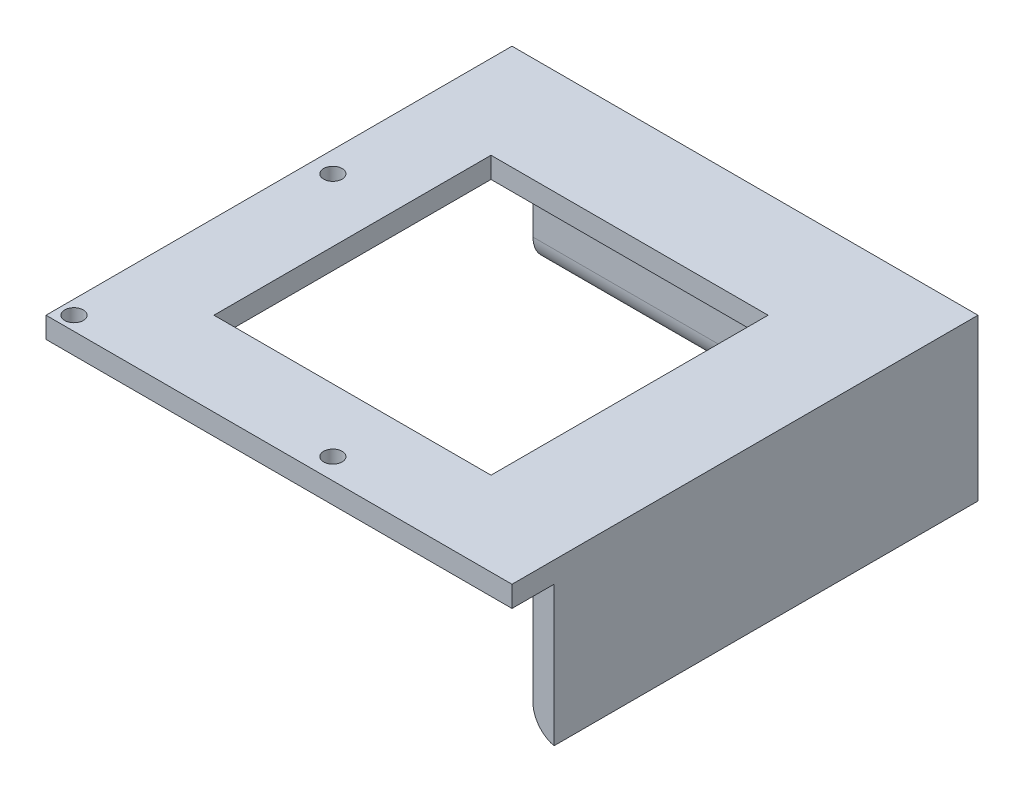
SolidWorks part; units mm, degrees
ref_plane "Front Plane" through (0, 0, 0) normal (0, 0, 1) x (1, 0, 0)
ref_plane "Top Plane" through (0, 0, 0) normal (0, 1, 0) x (1, 0, 0)
ref_plane "Right Plane" through (0, 0, 0) normal (1, 0, 0) x (0, 0, -1)
sketch "Sketch1" plane through (0, 0, 0) normal (0, 1, 0) x (1, 0, 0)
  line L9 (9.525, 9.525) -> (100.965, 9.525) construction
  line L10 (9.525, 9.525) -> (9.525, 100.965) construction
  line L11 (9.525, 100.965) -> (100.965, 100.965) construction
  line L12 (100.965, 9.525) -> (100.965, 100.965) construction
  line L16 (9.525, 100.965) -> (9.525, 105.7275) construction
  line L17 (0, 0) -> (105.7275, 0) construction
  line L18 (0, 0) -> (0, 105.7275) construction
  line L19 (0, 105.7275) -> (105.7275, 105.7275) construction
  line L20 (105.7275, 0) -> (105.7275, 105.7275) construction
  line L21 (100.965, 9.525) -> (105.7275, 9.525) construction
  dimension "D1" = 9.525
  dimension "D2" = 9.525
  dimension "D3" = 4.7625
  dimension "D4" = 4.7625
  dimension "D5" = 91.44
sketch "Sketch2" plane through (0, 0, 0) normal (0, 1, 0) x (1, 0, 0)
  line L8 (0, 105.7275) -> (105.7275, 105.7275) construction
  line L9 (0, 0) -> (0, 105.7275) construction
  line L10 (0, 0) -> (105.7275, 0) construction
  line L11 (105.7275, 0) -> (105.7275, 105.7275) construction
  line L12 (0, 105.7275) -> (105.7275, 105.7275)
  line L13 (0, 0) -> (0, 105.7275)
  line L14 (0, 0) -> (105.7275, 0)
  line L15 (105.7275, 0) -> (105.7275, 105.7275)
extrude "Boss-Extrude1" add sketch "Sketch2" along normal blind 4.7625
sketch "Sketch5" plane through (0, 0, 0) normal (0, 1, 0) x (1, 0, 0)
  line L0 (105.7275, 0) -> (105.7275, 105.7275) construction
  line L1 (100.965, 9.525) -> (105.7275, 9.525) construction
  line L2 (100.965, 9.525) -> (100.965, 100.965) construction
  line L3 (0, 105.7275) -> (105.7275, 105.7275) construction
  line L4 (9.525, 100.965) -> (100.965, 100.965) construction
  line L5 (9.525, 100.965) -> (9.525, 105.7275) construction
  line L6 (105.7275, 9.525) -> (105.7275, 105.7275)
  line L7 (100.965, 9.525) -> (105.7275, 9.525)
  line L8 (100.965, 9.525) -> (100.965, 100.965)
  line L9 (9.525, 105.7275) -> (105.7275, 105.7275)
  line L10 (9.525, 100.965) -> (100.965, 100.965)
  line L11 (9.525, 100.965) -> (9.525, 105.7275)
extrude "Boss-Extrude2" add sketch "Sketch5" against normal blind 31.75
sketch "Sketch6" plane through (0, 4.7625, 0) normal (0, 1, 0) x (1, 0, 0)
  line L0 (0, 0) -> (0, 105.7275) construction
  line L1 (0, 0) -> (105.7275, 0) construction
  line L2 (9.525, 9.525) -> (9.525, 100.965) construction
  line L3 (9.525, 9.525) -> (100.965, 9.525) construction
  circle A0 centre (3.175, 3.175) radius 2.1
  circle A1 centre (60.325, 4.7625) radius 2.1
  circle A2 centre (4.7625, 60.325) radius 2.1
  dimension "D7" = 4.2
  dimension "D1" = 4.7625
  dimension "D2" = 4.7625
  dimension "D3" = 3.175
  dimension "D4" = 3.175
  dimension "D5" = 50.8
  dimension "D6" = 50.8
extrude "Cut-Extrude1" cut sketch "Sketch6" against normal through all
fillet "Fillet1" radius 6.35 2 edges at (55.245, -31.75, -100.965) (100.965, -31.75, -55.245)
sketch "Sketch7" plane through (0, 0, 0) normal (0, -1, 0) x (1, 0, 0)
  line L20 (19.05, -81.915) -> (81.915, -81.915)
  line L21 (81.915, -81.915) -> (81.915, -19.05)
  line L22 (81.915, -19.05) -> (19.05, -19.05)
  line L23 (19.05, -19.05) -> (19.05, -81.915)
  line L24 (19.05, -81.915) -> (81.915, -81.915)
  line L25 (81.915, -81.915) -> (81.915, -19.05)
  line L26 (81.915, -19.05) -> (19.05, -19.05)
  line L27 (19.05, -19.05) -> (19.05, -81.915)
  dimension "D1" = 19.05
extrude "Cut-Extrude2" cut sketch "Sketch7" against normal through all
equation "\"D7@Sketch6\"=4.2mm"
